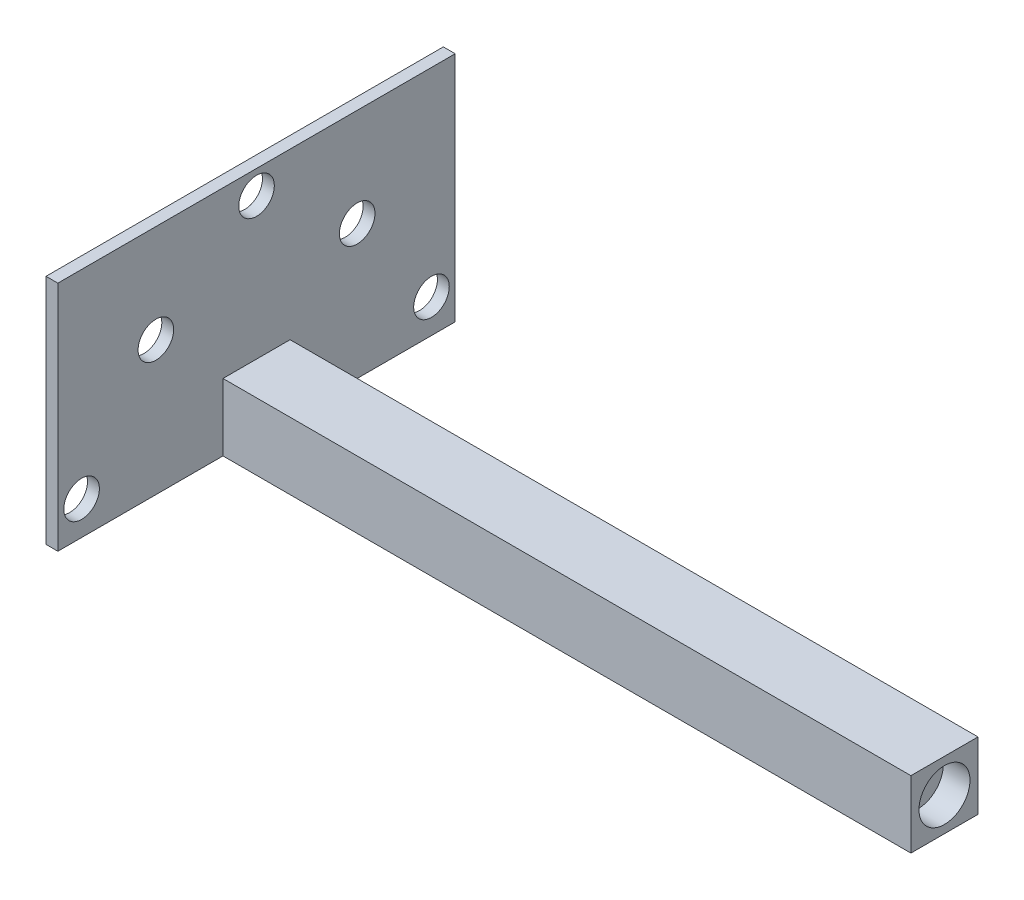
SolidWorks part; units mm, degrees
ref_plane "Front Plane" through (0, 0, 0) normal (0, 0, 1) x (1, 0, 0)
ref_plane "Top Plane" through (0, 0, 0) normal (0, 1, 0) x (1, 0, 0)
ref_plane "Right Plane" through (0, 0, 0) normal (1, 0, 0) x (0, 0, -1)
sketch "Sketch1" plane through (0, 0, 0) normal (1, 0, 0) x (0, 0, -1)
  line L0 (-8.4853, 8.4853) -> (-14.75, 0) construction
  line L1 (-8.4853, 8.4853) -> (0, 14.75) construction
  line L3 (-16.75, -2.8284) -> (16.75, -2.8284)
  line L4 (-16.75, -2.8284) -> (-16.75, 16.75)
  line L5 (-16.75, 16.75) -> (16.75, 16.75)
  line L6 (16.75, -2.8284) -> (16.75, 16.75)
  line L7 (-2.8284, -2.8284) -> (2.8284, -2.8284)
  line L8 (-2.8284, -2.8284) -> (-2.8284, 2.8284)
  line L9 (-2.8284, 2.8284) -> (2.8284, 2.8284)
  line L10 (2.8284, -2.8284) -> (2.8284, 2.8284)
  circle A0 centre (0, 0) radius 14.75 construction
  circle A1 centre (0, 14.75) radius 1.5
  circle A2 centre (0, 0) radius 14.75 construction
  circle A3 centre (14.75, 0) radius 1.5
  circle A4 centre (0, 0) radius 14.75 construction
  circle A5 centre (0, -14.75) radius 1.5 construction
  circle A6 centre (0, 0) radius 14.75 construction
  circle A7 centre (-14.75, 0) radius 1.5
  circle A8 centre (0, 0) radius 12 construction
  circle A9 centre (-8.4853, 8.4853) radius 1.5
  circle A10 centre (8.4853, 8.4853) radius 1.5
  circle A11 centre (8.4853, -8.4853) radius 1.5 construction
  circle A12 centre (-8.4853, -8.4853) radius 1.5 construction
  circle A13 centre (0, 0) radius 4 construction
  point P16 (0, 0)
  point P27 (0, 0)
  dimension "D1" = 4
  dimension "D2" = 4
  dimension "D3" = 2
  dimension "D6" = 3
  dimension "D7" = 8
  dimension "D8" = 29.5
  dimension "D9" = 24
  dimension "D4" = 2
  dimension "D5" = 2
extrude "Boss-Extrude1" add sketch "Sketch1" along normal blind 1 contours L3 L6 L5 L4 A10 A9 A7 A3 A1 | L3 L10 L9 L8 region at (0, 7.3763, 0) region at (0, 0, 0)
extrude "Boss-Extrude2" add sketch "Sketch1<3>" along normal blind 59 contours L3 L10 L9 L8 region at (0, 0, 0)
sketch "Sketch1<3>" plane through (0, 0, 0) normal (1, 0, 0) x (0, 0, -1) same geometry as "Sketch1"
sketch "Sketch3" plane through (59, 0, 0) normal (1, 0, 0) x (0, 0, -1)
  circle A1 centre (0, 0) radius 2.15
extrude "Cut-Extrude1" cut sketch "Sketch3" against normal blind 2.25 contours A1
